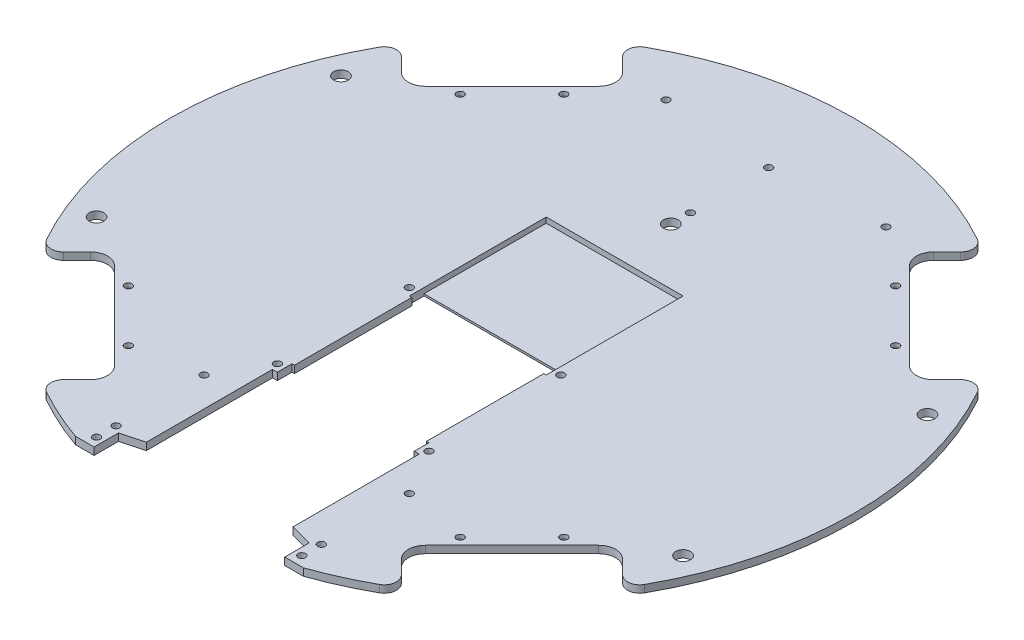
SolidWorks part; units mm, degrees
material "1060 Alloy"
ref_plane "Front Plane" through (0, 0, 0) normal (0, 0, 1) x (1, 0, 0)
ref_plane "Top Plane" through (0, 0, 0) normal (0, 1, 0) x (1, 0, 0)
ref_plane "Right Plane" through (0, 0, 0) normal (1, 0, 0) x (0, 0, -1)
sketch "Sketch1" plane through (0, 0, 0) normal (0, 1, 0) x (1, 0, 0)
  circle A0 centre (0, 0) radius 140
  dimension "D1" = 280
extrude "Boss-Extrude1" add sketch "Sketch1" along normal blind 3
sketch "Sketch7" plane through (0, 3, 0) normal (0, 1, 0) x (1, 0, 0)
  line L0 (-99.0303, -63.6043) -> (-63.6043, -99.0303)
  line L1 (-108.8591, -63.6043) -> (-121.6224, -76.3675)
  line L2 (-63.6043, -108.8591) -> (-76.3675, -121.6224)
  line L3 (-121.6224, -76.3675) -> (-76.3675, -121.6224)
  line L4 (0, 0) -> (-98.9949, -98.9949) construction
  line L7 (0, 0) -> (0, 130) construction
  circle A0 centre (0, 0) radius 140 construction
  arc A1 (-108.8591, -63.6043) -> (-99.0303, -63.6043) centre (-103.9447, -68.5186) cw
  arc A2 (-63.6043, -99.0303) -> (-63.6043, -108.8591) centre (-68.5186, -103.9447) cw
  dimension "D4" = 6.95
  dimension "D1" = 115
  dimension "D2" = 64
  dimension "D3" = 135
extrude "Cut-Extrude4" cut sketch "Sketch7" against normal up to next
sketch "Sketch9" plane through (0, 3, 0) normal (0, 1, 0) x (1, 0, 0)
  line L1 (-63.6043, -99.0303) -> (-99.0303, -63.6043) construction
  line L4 (-108.8591, -63.6043) -> (-119.0017, -73.7469) construction
  circle A0 centre (-89.0955, -67.8823) radius 1.5
  circle A1 centre (-67.8823, -89.0955) radius 1.5
  dimension "D4" = 3
  dimension "D1" = 4
  dimension "D2" = 30
  dimension "D3" = 17
  dimension "D5" = 4
extrude "Cut-Extrude6" cut sketch "Sketch9" against normal up to next
fillet "Fillet1" radius 5 2 edges at (-73.7469, 1.5, 119.0017) (-119.0017, 1.5, 73.7469)
pattern_circular "CirPattern1" count 4 over 360 about axis through (0, 3, 0) along (0, 1, 0) of "Cut-Extrude4", "Fillet1", "Cut-Extrude6"
sketch "Sketch2" plane through (0, 3, 0) normal (0, 1, 0) x (1, 0, 0)
  line L0 (-46.6476, -132) -> (-39, -132)
  line L1 (-30, -119.5885) -> (-30, -68)
  line L2 (-28, -8) -> (28, -8)
  line L3 (30, -68) -> (30, -119.5885)
  line L4 (39, -132) -> (46.6476, -132)
  line L5 (46.6476, -132) -> (46.6476, -140)
  line L6 (46.6476, -140) -> (-46.6476, -140)
  line L7 (-46.6476, -140) -> (-46.6476, -132)
  line L8 (-28, -62) -> (-28, -68)
  line L9 (-28, -68) -> (-30, -68)
  line L10 (28, -62) -> (28, -68)
  line L11 (28, -68) -> (30, -68)
  line L12 (-28, -62) -> (-27, -62)
  line L13 (-27, -62) -> (-27, -14)
  line L14 (-27, -14) -> (-28, -14)
  line L15 (-28, -14) -> (-28, -8)
  line L16 (28, -8) -> (28, -14)
  line L17 (28, -14) -> (27, -14)
  line L18 (27, -14) -> (27, -62)
  line L19 (27, -62) -> (28, -62)
  line L20 (-39, -132) -> (-39, -122)
  line L21 (-39, -122) -> (-30, -119.5885)
  line L22 (39, -132) -> (39, -122)
  line L23 (39, -122) -> (30, -119.5885)
  circle A0 centre (0, 0) radius 140 construction
  dimension "D8" = 1
  dimension "D5" = 60
  dimension "D6" = 56
  dimension "D1" = 8
  dimension "D2" = 124
  dimension "D3" = 60
  dimension "D4" = 16.6476
  dimension "D7" = 6
  dimension "D9" = 78
  dimension "D10" = 10
  dimension "D11" = 105
extrude "Cut-Extrude1" cut sketch "Sketch2" against normal up to next
fillet "Fillet3" radius 1.5 8 edges at (67.8823, 0, 90.5955) (89.0955, 0, 69.3823) (89.0955, 0, -66.3823) (67.8823, 0, -87.5955) (-67.8823, 0, -87.5955) (-89.0955, 0, -66.3823) (-67.8823, 0, 90.5955) (-89.0955, 0, 69.3823)
sketch "Sketch10" plane through (0, 3, 0) normal (0, 1, 0) x (1, 0, 0)
  circle A0 centre (-31, -65) radius 1.5
  circle A1 centre (31, -65) radius 1.5
  circle A2 centre (-31, -11) radius 1.5
  circle A3 centre (31, -11) radius 1.5
  dimension "D3" = 3
  dimension "D1" = 31
  dimension "D2" = 62
  dimension "D4" = 65
  dimension "D5" = 54
extrude "Cut-Extrude7" cut sketch "Sketch10" against normal up to next
sketch "Sketch13" plane through (0, 3, 0) normal (0, 1, 0) x (1, 0, 0)
  line L1 (-39, -132) -> (-46.6476, -132) construction
  circle A0 centre (-42, -84) radius 1.5
  circle A1 centre (-42, -120) radius 1.5
  circle A2 centre (42, -120) radius 1.5
  circle A3 centre (42, -84) radius 1.5
  dimension "D1" = 3
  dimension "D2" = 12
  dimension "D3" = 36
  dimension "D4" = 42
  dimension "D5" = 42
extrude "Cut-Extrude9" cut sketch "Sketch13" against normal up to next
sketch "Sketch16" plane through (0, 3, 0) normal (0, 1, 0) x (1, 0, 0)
  circle A0 centre (0, 73) radius 1.5
  circle A1 centre (-45, 108) radius 1.5
  circle A2 centre (45, 108) radius 1.5
  circle A3 centre (0, 105) radius 1.5
  circle A4 centre (0, 65) radius 3
  dimension "D2" = 3
  dimension "D5" = 6
  dimension "D1" = 73
  dimension "D3" = 108
  dimension "D4" = 90
  dimension "D6" = 32
  dimension "D7" = 65
extrude "Cut-Extrude12" cut sketch "Sketch16" against normal up to next
sketch "Sketch17" plane through (0, 3, 0) normal (0, 1, 0) x (1, 0, 0)
  circle A0 centre (-120, 50) radius 3
  circle A1 centre (-120, -50) radius 3
  circle A2 centre (120, 50) radius 3
  circle A3 centre (120, -50) radius 3
  dimension "D1" = 6
  dimension "D2" = 50
  dimension "D3" = 50
  dimension "D4" = 120
  dimension "D5" = 120
extrude "Cut-Extrude13" cut sketch "Sketch17" against normal up to next
sketch "Sketch18" plane through (0, 3, 0) normal (0, 1, 0) x (1, 0, 0)
  line L0 (-28, -8) -> (-28, -14) construction
  line L1 (-28, -8) -> (28, -8)
  line L2 (-28, -8) -> (-28, 42)
  line L3 (-28, 42) -> (28, 42)
  line L4 (28, -8) -> (28, 42)
  line L5 (28, -8) -> (-28, -8) construction
  line L6 (28, -8) -> (-28, -8) construction
  dimension "D1" = 50
extrude "Cut-Extrude14" cut sketch "Sketch18" against normal blind 2.2
sketch "Sketch19" plane through (0, 3, 0) normal (0, 1, 0) x (1, 0, 0)
  line L0 (-39, -122) -> (-39, -132) construction
  line L1 (-39, -132) -> (-46.6476, -132) construction
  line L2 (39, -132) -> (39, -122) construction
  circle A0 centre (-42, -128) radius 1.5
  circle A1 centre (42, -128) radius 1.5
  dimension "D4" = 3
  dimension "D1" = 3
  dimension "D2" = 4
  dimension "D3" = 3
extrude "Cut-Extrude15" cut sketch "Sketch19" against normal up to next
